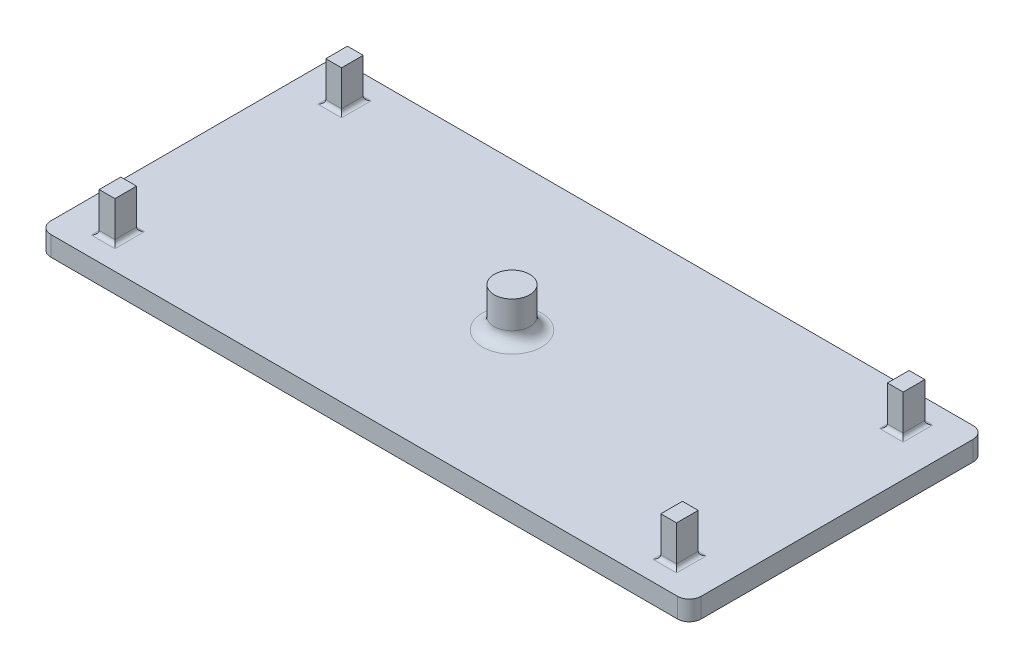
SolidWorks part; units mm, degrees
ref_plane "Front Plane" through (0, 0, 0) normal (0, 0, 1) x (1, 0, 0)
ref_plane "Top Plane" through (0, 0, 0) normal (0, 1, 0) x (1, 0, 0)
ref_plane "Right Plane" through (0, 0, 0) normal (1, 0, 0) x (0, 0, -1)
sketch "Sketch1" plane through (0, 0, 0) normal (0, 1, 0) x (1, 0, 0)
  line L1 (-82.5, 37.5) -> (82.5, 37.5)
  line L2 (-82.5, 37.5) -> (-82.5, -37.5)
  line L3 (-82.5, -37.5) -> (82.5, -37.5)
  line L4 (82.5, 37.5) -> (82.5, -37.5)
  line L5 (-82.5, 37.5) -> (82.5, -37.5) construction
  line L6 (-82.5, -37.5) -> (82.5, 37.5) construction
  point P0 (0, 0)
  dimension "D1" = 165
  dimension "D2" = 75
extrude "Boss-Extrude1" add sketch "Sketch1" along normal blind 5
sketch "Sketch3" plane through (0, 5, 0) normal (0, 1, 0) x (1, 0, 0)
  line L5 (82.5, -37.5) -> (82.5, 37.5) construction
  line L6 (-82.5, -37.5) -> (82.5, -37.5) construction
  line L8 (76.25, -37.5) -> (66.25, -37.5)
  line L13 (0, -2.75) -> (0, 2.75) construction
  line L14 (-73.25, 26) -> (-73.25, 31.5)
  line L19 (-73.25, 31.5) -> (-69.25, 31.5)
  line L20 (-69.25, 26) -> (-69.25, 31.5)
  line L25 (-73.25, 26) -> (-69.25, 26)
  line L26 (-73.25, -31.5) -> (-73.25, -26)
  line L27 (76.25, -37.5) -> (76.25, 37.5)
  line L28 (76.25, 37.5) -> (66.25, 37.5)
  line L29 (66.25, -37.5) -> (66.25, 37.5)
  line L30 (76.25, -37.5) -> (66.25, 37.5) construction
  line L31 (76.25, 37.5) -> (66.25, -37.5) construction
  line L32 (76.25, -20) -> (66.25, -20)
  line L33 (76.25, -20) -> (76.25, 20)
  line L34 (76.25, 20) -> (66.25, 20)
  line L35 (66.25, -20) -> (66.25, 20)
  line L36 (76.25, -20) -> (66.25, 20) construction
  line L37 (76.25, 20) -> (66.25, -20) construction
  line L38 (73.25, -31.5) -> (69.25, -31.5)
  line L39 (73.25, -31.5) -> (73.25, -26)
  line L40 (73.25, -26) -> (69.25, -26)
  line L41 (69.25, -31.5) -> (69.25, -26)
  line L42 (73.25, -31.5) -> (69.25, -26) construction
  line L43 (73.25, -26) -> (69.25, -31.5) construction
  line L44 (73.25, 26) -> (69.25, 26)
  line L45 (73.25, 26) -> (73.25, 31.5)
  line L46 (73.25, 31.5) -> (69.25, 31.5)
  line L47 (69.25, 26) -> (69.25, 31.5)
  line L48 (73.25, 26) -> (69.25, 31.5) construction
  line L49 (73.25, 31.5) -> (69.25, 26) construction
  line L50 (-73.25, -26) -> (-69.25, -26)
  line L51 (-69.25, -31.5) -> (-69.25, -26)
  line L52 (-73.25, -31.5) -> (-69.25, -31.5)
  line L53 (-76.25, -37.5) -> (-76.25, 37.5)
  line L54 (-76.25, 37.5) -> (-66.25, 37.5)
  line L55 (-66.25, -37.5) -> (-66.25, 37.5)
  line L56 (-76.25, -37.5) -> (-66.25, -37.5)
  line L57 (-76.25, -20) -> (-76.25, 20)
  line L58 (-76.25, 20) -> (-66.25, 20)
  line L59 (-66.25, -20) -> (-66.25, 20)
  line L60 (-76.25, -20) -> (-66.25, -20)
  circle A0 centre (0, 0) radius 4.5
  point P29 (71.25, 0)
  point P34 (71.25, 0)
  point P39 (71.25, -26)
  point P40 (71.25, -28.75)
  point P45 (71.25, 28.75)
  dimension "D1" = 9
  dimension "D3" = 6.25
  dimension "D15" = 75
  dimension "D16" = 10
  dimension "D17" = 40
  dimension "D18" = 6
  dimension "D19" = 6
  dimension "D20" = 3
  dimension "D21" = 3
  dimension "D22" = 6
  dimension "D23" = 6
  dimension "D24" = 3
  dimension "D25" = 3
extrude "Boss-Extrude3" add sketch "Sketch3" along normal blind 10 contours A0 | L14 L25 L20 L19 | L40 L41 L38 L39 | L46 L47 L44 L45 | L50 L51 L52 L26 region at (-71.25, 5, -28.75) region at (0, 5, 0)
fillet "Fillet2" radius 3 1 edges at (0, 5, 4.5)
fillet "Fillet4" radius 3 4 edges at (-82.5, 2.5, -37.5) (82.5, 2.5, 37.5) (82.5, 2.5, -37.5) (-82.5, 2.5, 37.5)
fillet "Fillet5" radius 1 16 edges at (-73.25, 5, 28.75) (-71.25, 5, 26) (-69.25, 5, 28.75) (-71.25, 5, 31.5) (-71.25, 5, -26) (-73.25, 5, -28.75) (-71.25, 5, -31.5) (-69.25, 5, -28.75) (73.25, 5, -28.75) (71.25, 5, -31.5) (69.25, 5, -28.75) (71.25, 5, -26) (71.25, 5, 31.5) (69.25, 5, 28.75) (73.25, 5, 28.75) (71.25, 5, 26)
sketch "Sketch4" plane through (0, 0, 0) normal (0, -1, 0) x (1, 0, 0)
  line L0 (79.5, -37.5) -> (-79.5, -37.5) construction
  line L1 (-79.5, 37.5) -> (79.5, 37.5) construction
  line L2 (-82.5, -34.5) -> (-82.5, 34.5) construction
  line L3 (0, -8.25) -> (0, 8.25) construction
  circle A0 centre (-22.5, -32.5) radius 4.5
  circle A1 centre (-22.5, 32.5) radius 4.5
  circle A2 centre (22.5, 32.5) radius 4.5
  circle A3 centre (22.5, -32.5) radius 4.5
  point P10 (0, 0)
  dimension "D1" = 9
  dimension "D2" = 5
  dimension "D3" = 5
  dimension "D4" = 60
extrude "Cut-Extrude1" cut sketch "Sketch4" against normal blind 2
